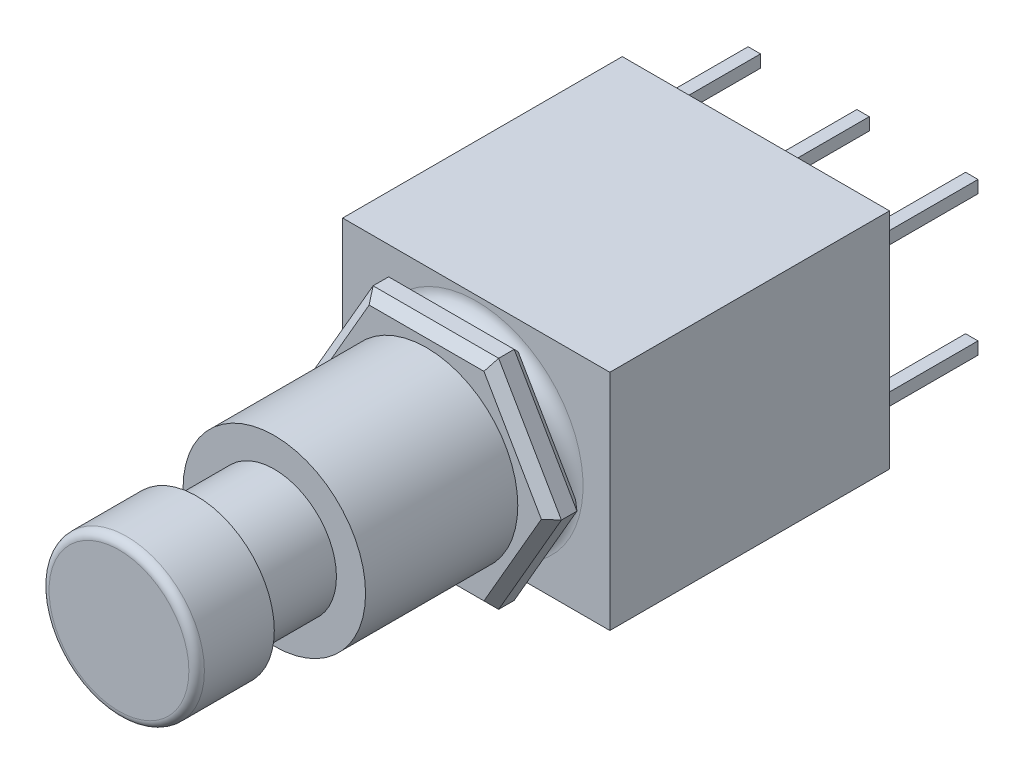
SolidWorks part; units mm, degrees
ref_plane "Front Plane" through (0, 0, 0) normal (0, 0, 1) x (1, 0, 0)
ref_plane "Top Plane" through (0, 0, 0) normal (0, 1, 0) x (1, 0, 0)
ref_plane "Right Plane" through (0, 0, 0) normal (1, 0, 0) x (0, 0, -1)
sketch "Sketch1" plane through (0, 0, 0) normal (0, 0, 1) x (1, 0, 0)
  line L1 (0, 0) -> (17.2, 0)
  line L2 (0, 0) -> (0, 14.4)
  line L3 (0, 14.4) -> (17.2, 14.4)
  line L4 (17.2, 0) -> (17.2, 14.4)
  dimension "D1" = 17.2
  dimension "D2" = 14.4
extrude "Boss-Extrude1" add sketch "Sketch1" along normal blind 18
sketch "Sketch2" plane through (0, 0, 18) normal (0, 0, 1) x (1, 0, 0)
  line L0 (8.6, 14.4) -> (8.6, 0) construction
  line L1 (17.2, 14.4) -> (0, 14.4) construction
  line L2 (0, 0) -> (17.2, 0) construction
  line L4 (0, 14.4) -> (0, 0) construction
  line L5 (0, 7.2) -> (17.2, 7.2) construction
  line L6 (17.2, 0) -> (17.2, 14.4) construction
  circle A0 centre (8.6, 7.2) radius 5.875
  dimension "D1" = 11.75
extrude "Boss-Extrude2" add sketch "Sketch2" along normal blind 13
sketch "Sketch3" plane through (0, 0, 31) normal (0, 0, 1) x (1, 0, 0)
  circle A0 centre (8.6, 7.2) radius 4
  dimension "D1" = 8
extrude "Boss-Extrude3" add sketch "Sketch3" along normal blind 5
sketch "Sketch4" plane through (0, 0, 36) normal (0, 0, 1) x (1, 0, 0)
  circle A0 centre (8.6, 7.2) radius 5
  dimension "D1" = 10
extrude "Boss-Extrude4" add sketch "Sketch4" along normal blind 5
sketch "Sketch5" plane through (0, 0, 0) normal (0, 0, -1) x (-1, 0, 0)
  line L0 (-8.6, 14.4) -> (-8.6, 0) construction
  line L1 (-17.2, 14.4) -> (0, 14.4) construction
  line L2 (0, 0) -> (-17.2, 0) construction
  line L4 (-17.2, 0) -> (-17.2, 14.4) construction
  line L5 (-17.2, 7.2) -> (0, 7.2) construction
  line L6 (0, 14.4) -> (0, 0) construction
  line L7 (-3.6, 3.45) -> (-13.6, 3.45)
  line L8 (-3.6, 3.45) -> (-3.6, 10.95)
  line L9 (-3.6, 10.95) -> (-13.6, 10.95)
  line L10 (-13.6, 3.45) -> (-13.6, 10.95)
  line L11 (-3.6, 3.45) -> (-13.6, 10.95) construction
  line L12 (-3.6, 10.95) -> (-13.6, 3.45) construction
  point P6 (-8.6, 7.2)
  dimension "D1" = 10
  dimension "D2" = 7.5
extrude "Boss-Extrude5" add sketch "Sketch5" along normal blind 1.2
sketch "Sketch6" plane through (0, 0, 0) normal (0, 0, -1) x (-1, 0, 0)
  line L0 (-8.6, 14.4) -> (-8.6, 0) construction
  line L1 (-17.2, 14.4) -> (0, 14.4) construction
  line L2 (0, 0) -> (-17.2, 0) construction
  line L4 (-17.2, 0) -> (-17.2, 14.4) construction
  line L5 (-17.2, 7.2) -> (0, 7.2) construction
  line L6 (0, 14.4) -> (0, 0) construction
  line L7 (-15.6, 11.7) -> (-1.6, 11.7) construction
  line L8 (-15.6, 11.7) -> (-15.6, 2.7) construction
  line L10 (-1.6, 11.7) -> (-1.6, 2.7) construction
  line L11 (-16, 11.3) -> (-15.2, 11.3)
  line L12 (-16, 11.3) -> (-16, 12.1)
  line L13 (-16, 12.1) -> (-15.2, 12.1)
  line L14 (-15.2, 11.3) -> (-15.2, 12.1)
  line L15 (-16, 11.3) -> (-15.2, 12.1) construction
  line L16 (-16, 12.1) -> (-15.2, 11.3) construction
  point P16 (-1.6, 7.2)
  point P18 (-8.6, 11.7)
  dimension "D2" = 14
  dimension "D3" = 0.8
extrude "Boss-Extrude6" add sketch "Sketch6" along normal blind 7.3
chamfer "Chamfer1" distance 0.4 angle 45 4 edges at (15.6, 11.3, -7.3) (16, 11.7, -7.3) (15.6, 12.1, -7.3) (15.2, 11.7, -7.3)
fillet "Fillet1" radius 1 1 edges at (2.725, 7.2, 18)
fillet "Fillet2" radius 0.5 1 edges at (13.6, 7.2, 41)
ref_plane "Plane1" through (0, 0, 19) normal (0, 0, 1) x (1, 0, 0)
sketch "Sketch7" plane through (0, 0, 19) normal (0, 0, 1) x (1, 0, 0)
  line L1 (16.6829, 7.2) -> (12.6415, 14.2)
  line L2 (12.6415, 14.2) -> (4.5585, 14.2)
  line L3 (4.5585, 14.2) -> (0.5171, 7.2)
  line L4 (0.5171, 7.2) -> (4.5585, 0.2)
  line L5 (4.5585, 0.2) -> (12.6415, 0.2)
  line L6 (12.6415, 0.2) -> (16.6829, 7.2)
  circle A0 centre (8.6, 7.2) radius 5.875
  circle A1 centre (8.6, 7.2) radius 7 construction
  dimension "D1" = 11.75
  dimension "D2" = 14
extrude "Boss-Extrude7" add sketch "Sketch7" along normal blind 2.2
chamfer "Chamfer2" distance 0.6 angle 45 12 edges at (14.6622, 10.7, 19) (14.6622, 3.7, 19) (8.6, 0.2, 19) (2.5378, 3.7, 19) (2.5378, 10.7, 19) (8.6, 14.2, 19) (14.6622, 10.7, 21.2) (14.6622, 3.7, 21.2) (8.6, 0.2, 21.2) (2.5378, 3.7, 21.2) (2.5378, 10.7, 21.2) (8.6, 14.2, 21.2)
pattern_linear "LPattern1" count 3 spacing 7 along (-1, 0, 0) count 2 spacing 9 along (0, -1, 0) of "Boss-Extrude6", "Chamfer1"
